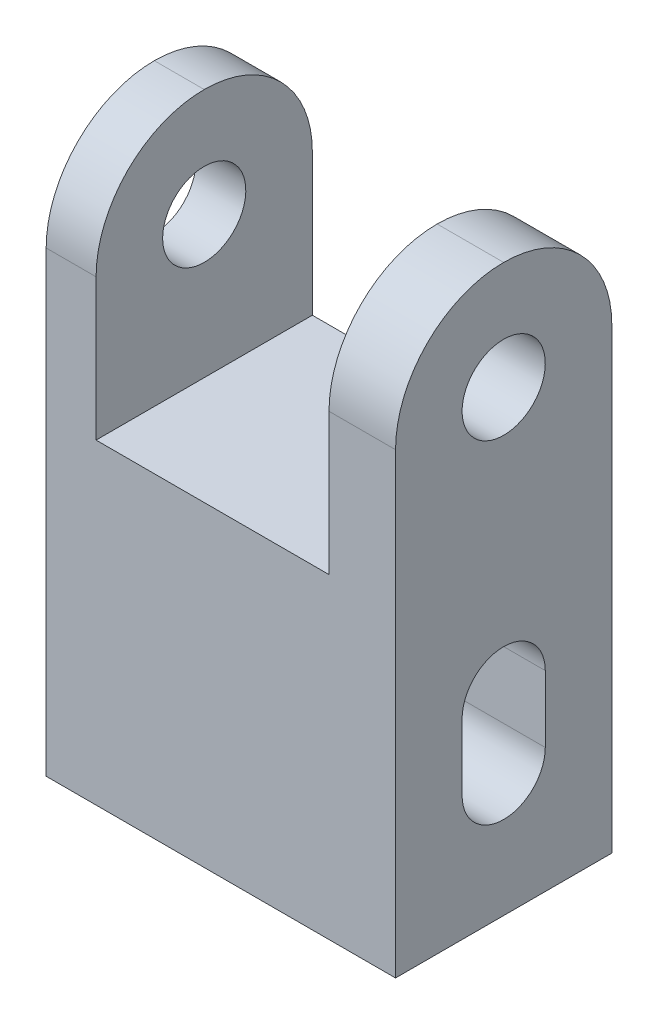
SolidWorks part; units mm, degrees
ref_plane "Ön Düzlem" through (0, 0, 0) normal (0, 0, 1) x (1, 0, 0)
ref_plane "Üst Düzlem" through (0, 0, 0) normal (0, 1, 0) x (1, 0, 0)
ref_plane "Sağ Düzlem" through (0, 0, 0) normal (1, 0, 0) x (0, 0, -1)
sketch "Sketch2" plane through (0, 0, 0) normal (0, 0, 1) x (1, 0, 0)
  line L0 (0, 0) -> (0, -34)
  line L1 (0, -34) -> (21, -34)
  line L2 (21, -34) -> (21, 0)
  line L3 (21, 0) -> (17, 0)
  line L4 (17, 0) -> (17, -15)
  line L5 (17, -15) -> (3, -15)
  line L6 (3, -15) -> (3, 0)
  line L7 (3, 0) -> (0, 0)
  line L8 (10.5, -34) -> (10.5, -21.5) construction
  dimension "D1" = 14
  dimension "D2" = 4
  dimension "D3" = 3
  dimension "D4" = 15
  dimension "D5" = 34
extrude "Boss-Extrude1" add sketch "Sketch2" along normal blind 13
sketch "Sketch4" plane through (0, 0, 0) normal (-1, 0, 0) x (0, 0, 1)
  line L0 (13, -34) -> (0, -34) construction
  line L1 (0, 0) -> (0, -34) construction
  line L2 (6.5, -24.5) -> (0, -24.5) construction
  line L3 (6.5, -26.5) -> (6.5, -22.5) construction
  line L4 (4, -26.5) -> (4, -22.5)
  line L5 (9, -26.5) -> (9, -22.5)
  arc A0 (4, -26.5) -> (9, -26.5) centre (6.5, -26.5) ccw
  arc A1 (9, -22.5) -> (4, -22.5) centre (6.5, -22.5) ccw
  point P8 (6.5, -24.5)
  dimension "D2" = 2
  dimension "D4" = 2.5
  dimension "D1" = 9.5
  dimension "D3" = 6.5
extrude "Cut-Extrude1" cut sketch "Sketch4" against normal through all contours L5 A1 L4 A0
sketch "Sketch5" plane through (21, 0, 0) normal (1, 0, 0) x (0, 0, -1)
  line L3 (0, -34) -> (0, 0) construction
  line L4 (-13, 0) -> (0, 0) construction
  circle A0 centre (-6.5, -6.5) radius 2.5
  dimension "D2" = 5
  dimension "D1" = 6.5
  dimension "D4" = 6.5
extrude "Cut-Extrude2" cut sketch "Sketch5" against normal through all and the other way through all
fillet "Fillet1" radius 6.5 4 edges at (19, 0, 13) (1.5, 0, 13) (1.5, 0, 0) (19, 0, 0)
sketch "Sketch6" plane through (0, -34, 0) normal (0, -1, 0) x (1, 0, 0)
  line L0 (0, 6.5) -> (21, 6.5) construction
  line L1 (0, 13) -> (0, 0) construction
  line L2 (21, 13) -> (21, 0) construction
  circle A0 centre (10.5, 6.5) radius 2
  dimension "D1" = 4
extrude "Cut-Extrude3" cut sketch "Sketch6" against normal blind 8
